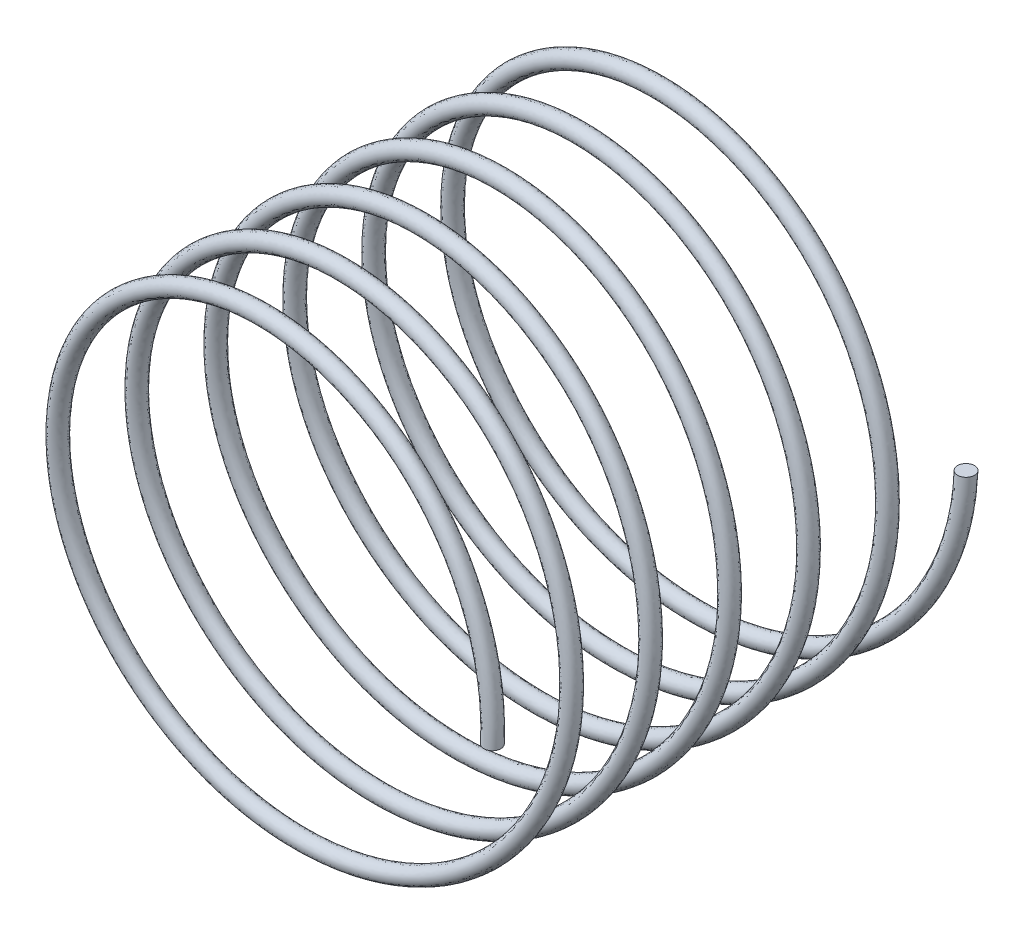
SolidWorks part; units mm, degrees
ref_plane "Face" through (0, 0, 0) normal (0, 0, 1) x (1, 0, 0)
ref_plane "Dessus" through (0, 0, 0) normal (0, 1, 0) x (1, 0, 0)
ref_plane "Droite" through (0, 0, 0) normal (1, 0, 0) x (0, 0, -1)
sketch "Esquisse1" plane through (0, 0, 0) normal (0, 0, 1) x (1, 0, 0)
  circle A0 centre (0, 0) radius 2.8
  dimension "D1" = 5.6
curve "Hélice/Spirale2" pitch 0.9333 height 5.6 radius 2.8 left hand yes centre (0, 0, 0) axis (0, 0, 1) start towards (1, 0, 0)
sketch "Esquisse2" plane through (0, 0, 0) normal (0, 1, 0) x (1, 0, 0)
  line L0 (0, -1.8205) -> (0, 4.0941) construction
  circle A0 centre (2.8, 0) radius 0.1
  spline S0 degree 3 poles (2.8, 0) (2.8, -0.0193) (2.6542, -0.0584) (2.0314, -0.1167) (1.0994, -0.175) (0, -0.2333) (-1.0994, -0.2917) (-2.0314, -0.35) (-2.6542, -0.4083) (-2.8729, -0.4667) (-2.6542, -0.525) (-2.0314, -0.5833) (-1.0994, -0.6417) (0, -0.7) (1.0994, -0.7583) (2.0314, -0.8167) (2.6542, -0.875) (2.8729, -0.9333) (2.6542, -0.9917) (2.0314, -1.05) (1.0994, -1.1083) (0, -1.1667) (-1.0994, -1.225) (-2.0314, -1.2833) (-2.6542, -1.3417) (-2.8729, -1.4) (-2.6542, -1.4583) (-2.0314, -1.5167) (-1.0994, -1.575) (0, -1.6333) (1.0994, -1.6917) (2.0314, -1.75) (2.6542, -1.8083) (2.8729, -1.8667) (2.6542, -1.925) (2.0314, -1.9833) (1.0994, -2.0417) (0, -2.1) (-1.0994, -2.1583) (-2.0314, -2.2167) (-2.6542, -2.275) (-2.8729, -2.3333) (-2.6542, -2.3917) (-2.0314, -2.45) (-1.0994, -2.5083) (0, -2.5667) (1.0994, -2.625) (2.0314, -2.6833) (2.6542, -2.7417) (2.8729, -2.8) (2.6542, -2.8583) (2.0314, -2.9167) (1.0994, -2.975) (0, -3.0333) (-1.0994, -3.0917) (-2.0314, -3.15) (-2.6542, -3.2083) (-2.8729, -3.2667) (-2.6542, -3.325) (-2.0314, -3.3833) (-1.0994, -3.4417) (0, -3.5) (1.0994, -3.5583) (2.0314, -3.6167) (2.6542, -3.675) (2.8729, -3.7333) (2.6542, -3.7917) (2.0314, -3.85) (1.0994, -3.9083) (0, -3.9667) (-1.0994, -4.025) (-2.0314, -4.0833) (-2.6542, -4.1417) (-2.8729, -4.2) (-2.6542, -4.2583) (-2.0314, -4.3167) (-1.0994, -4.375) (0, -4.4333) (1.0994, -4.4917) (2.0314, -4.55) (2.6542, -4.6083) (2.8729, -4.6667) (2.6542, -4.725) (2.0314, -4.7833) (1.0994, -4.8417) (0, -4.9) (-1.0994, -4.9583) (-2.0314, -5.0167) (-2.6542, -5.075) (-2.8729, -5.1333) (-2.6542, -5.1917) (-2.0314, -5.25) (-1.0994, -5.3083) (0, -5.3667) (1.0994, -5.425) (2.0314, -5.4833) (2.6542, -5.5416) (2.8, -5.5807) (2.8, -5.6) knots 0 0 0 0 0.010417 0.020833 0.03125 0.041667 0.052083 0.0625 0.072917 0.083333 0.09375 0.104167 0.114583 0.125 0.135417 0.145833 0.15625 0.166667 0.177083 0.1875 0.197917 0.208333 0.21875 0.229167 0.239583 0.25 0.260417 0.270833 0.28125 0.291667 0.302083 0.3125 0.322917 0.333333 0.34375 0.354167 0.364583 0.375 0.385417 0.395833 0.40625 0.416667 0.427083 0.4375 0.447917 0.458333 0.46875 0.479167 0.489583 0.5 0.510417 0.520833 0.53125 0.541667 0.552083 0.5625 0.572917 0.583333 0.59375 0.604167 0.614583 0.625 0.635417 0.645833 0.65625 0.666667 0.677083 0.6875 0.697917 0.708333 0.71875 0.729167 0.739583 0.75 0.760417 0.770833 0.78125 0.791667 0.802083 0.8125 0.822917 0.833333 0.84375 0.854167 0.864583 0.875 0.885417 0.895833 0.90625 0.916667 0.927083 0.9375 0.947917 0.958333 0.96875 0.979167 0.989583 1 1 1 1 construction
  dimension "D1" = 0.2
sweep "Balayage1" add profiles "Esquisse2" path "Hélice/Spirale2"
